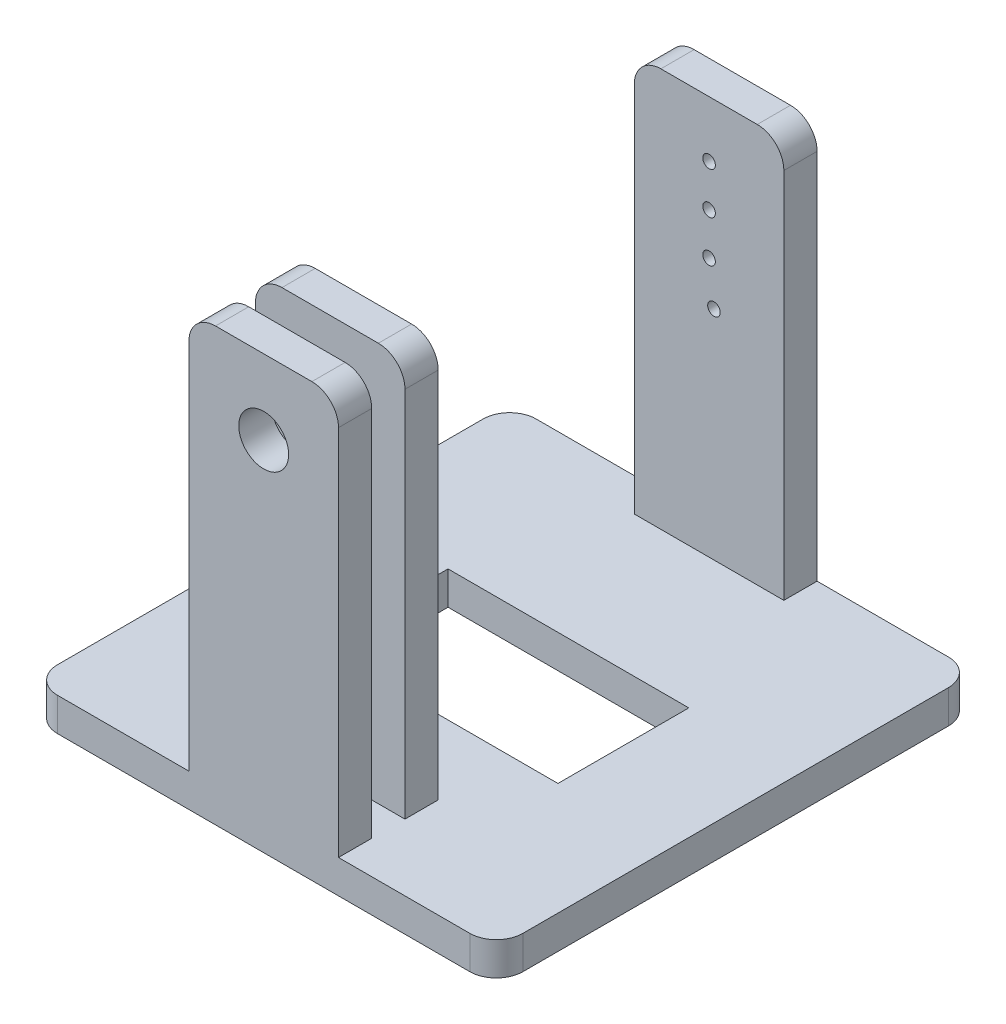
SolidWorks part; units mm, degrees
material "6061 Alloy"
ref_plane "Front Plane" through (0, 0, 0) normal (0, 0, 1) x (1, 0, 0)
ref_plane "Top Plane" through (0, 0, 0) normal (0, 1, 0) x (1, 0, 0)
ref_plane "Right Plane" through (0, 0, 0) normal (1, 0, 0) x (0, 0, -1)
sketch "Sketch1" plane through (0, 0, 0) normal (0, 1, 0) x (1, 0, 0)
  line L0 (19.7243, -19.7321) -> (19.7243, 25.9879)
  line L1 (19.7243, 25.9879) -> (-24.7257, 25.9879)
  line L2 (-24.7257, 25.9879) -> (-24.7257, -19.7321)
  line L3 (-24.7257, -19.7321) -> (19.7243, -19.7321)
  line L5 (-14.0007, -3.1221) -> (8.9993, -3.1221)
  line L6 (-14.0007, -3.1221) -> (-14.0007, 9.3779)
  line L7 (-14.0007, 9.3779) -> (8.9993, 9.3779)
  line L8 (8.9993, -3.1221) -> (8.9993, 9.3779)
  line L9 (-14.0007, -3.1221) -> (8.9993, 9.3779) construction
  line L10 (-14.0007, 9.3779) -> (8.9993, -3.1221) construction
  point P0 (8.9993, 3.1279)
  point P1 (19.7243, 3.1279)
  point P2 (-2.5007, -3.1221)
  point P3 (-2.5007, -19.7321)
  point P14 (-2.5007, 9.3779)
  point P15 (-2.5007, 25.9879)
  dimension "D1" = 23
  dimension "D2" = 12.5
  dimension "D3" = 45.72
  dimension "D4" = 44.45
extrude "Boss-Extrude1" add sketch "Sketch1" along normal blind 3.175
sketch "Sketch4" plane through (0, 3.175, 0) normal (0, 1, 0) x (1, 0, 0)
  line L0 (-24.7257, 3.1279) -> (19.7243, 3.1279) construction
  line L1 (-24.7257, 25.9879) -> (-24.7257, -19.7321) construction
  line L2 (19.7243, -19.7321) -> (19.7243, 25.9879) construction
  line L3 (-2.5007, 25.9879) -> (-2.5007, -23.8438) construction
  line L4 (19.7243, 25.9879) -> (-24.7257, 25.9879) construction
sketch "Sketch5" plane through (0, 0, 0) normal (1, 0, 0) x (0, 0, -1)
  line L0 (-19.7321, 3.175) -> (-19.7321, 41.275)
  line L1 (-19.7321, 41.275) -> (-16.5571, 41.275)
  line L2 (-16.5571, 41.275) -> (-16.5571, 3.175)
  line L3 (25.9879, 3.175) -> (25.9879, 41.275)
  line L4 (-16.5571, 3.175) -> (-19.7321, 3.175)
  line L5 (-13.3821, 3.175) -> (-13.3821, 41.275)
  line L6 (-13.3821, 41.275) -> (-10.2071, 41.275)
  line L7 (-10.2071, 41.275) -> (-10.2071, 3.175)
  line L8 (-13.3821, 3.175) -> (-10.2071, 3.175)
  line L9 (-19.7321, 3.175) -> (25.9879, 3.175) construction
  line L10 (25.9879, 41.275) -> (22.8129, 41.275)
  line L11 (-19.7321, 3.175) -> (-19.7321, 0) construction
  line L12 (22.8129, 41.275) -> (22.8129, 3.175)
  line L13 (25.9879, 3.175) -> (-23.8438, 3.175) construction
  line L14 (22.8129, 3.175) -> (25.9879, 3.175)
  dimension "D1" = 38.1
  dimension "D2" = 38.1
  dimension "D3" = 3.175
  dimension "D4" = 3.175
  dimension "D5" = 3.175
  dimension "D6" = 3.175
extrude "Boss-Extrude2" add sketch "Sketch5" along normal mid plane 14.2875 from vertex starting at point (-2.5007, 3.175, 23.8438)
sketch "Sketch6" plane through (0, 0, 19.7321) normal (0, 0, 1) x (1, 0, 0)
  line L0 (-2.5007, 41.275) -> (-2.5007, 31.75) construction
  line L1 (4.6431, 41.275) -> (-9.6444, 41.275) construction
  circle A0 centre (-2.5007, 34.1312) radius 2.3813
  point P8 (-2.5007, 36.5125)
  dimension "D2" = 4.7625
  dimension "D1" = 4.7625
extrude "Cut-Extrude2" cut sketch "Sketch6" against normal up to surface (9.525 mm away) up to face at (-2.5007, 22.225, 10.2071)
fillet "Fillet1" radius 2.54 10 edges at (19.7243, 1.5875, 19.7321) (19.7243, 1.5875, -25.9879) (-24.7257, 1.5875, 19.7321) (-24.7257, 1.5875, -25.9879) (-9.6444, 41.275, 18.1446) (-9.6444, 41.275, 11.7946) (4.6431, 41.275, 11.7946) (4.6431, 41.275, 18.1446) (-9.6444, 41.275, -24.4004) (4.6431, 41.275, -24.4004)
sketch "Sketch2" plane through (0, 0, -25.9879) normal (0, 0, -1) x (-1, 0, 0)
  line L0 (2.5007, 0) -> (2.5007, 3.175)
  line L1 (-17.1843, 0) -> (22.1857, 0) construction
  line L2 (-19.7243, 3.175) -> (24.7257, 3.175) construction
sketch "Sketch7" plane through (0, 0, -25.9879) normal (0, 0, -1) x (-1, 0, 0)
  line L3 (2.5007, 41.275) -> (2.5007, 3.175) construction
  line L4 (-2.1031, 41.275) -> (7.1044, 41.275) construction
  line L5 (-17.1843, 3.175) -> (-4.6431, 3.175) construction
  circle A2 centre (2.0333, 23.9399) radius 0.6
  circle A3 centre (2.5007, 27.9125) radius 0.6
  circle A4 centre (2.5007, 31.9125) radius 0.6
  circle A5 centre (2.5007, 35.9125) radius 0.6
  point P0 (2.5007, 36.5125)
  dimension "D5" = 1.2
  dimension "D1" = 4.7625
  dimension "D2" = 4
  dimension "D3" = 4
  dimension "D4" = 4
extrude "Cut-Extrude3" cut sketch "Sketch7" against normal up to next
